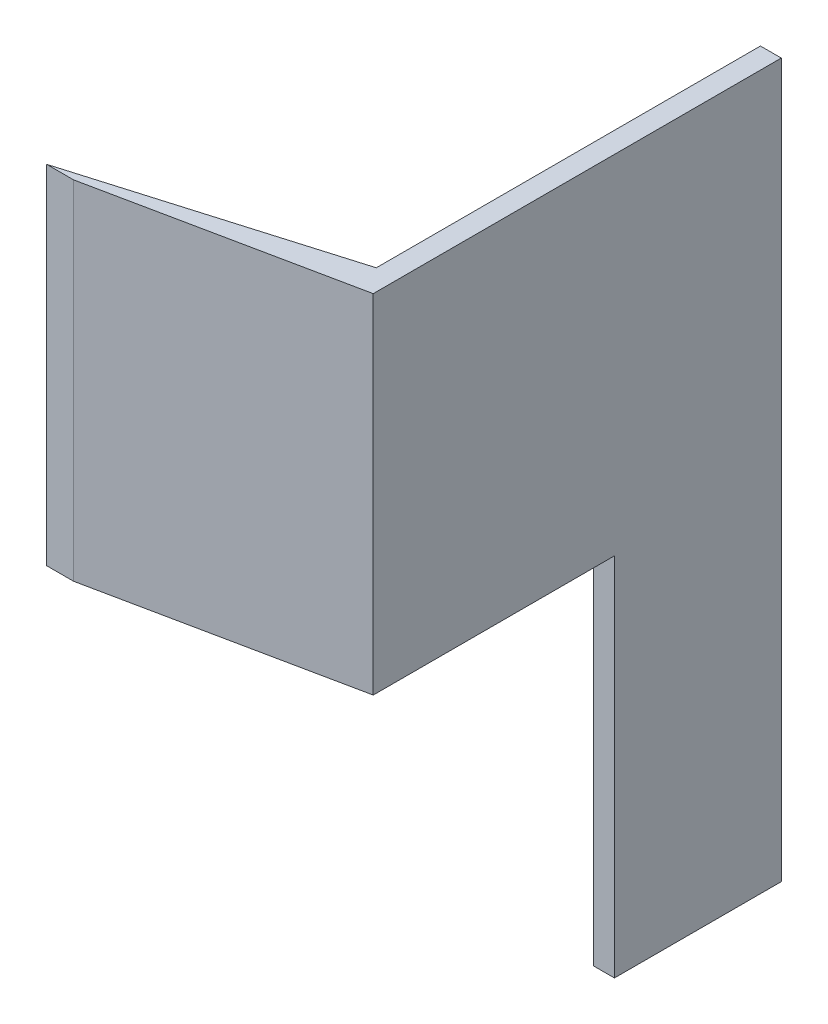
SolidWorks part; units mm, degrees
material "Perspex (TM) GS Acrylic Cast Sheet"
ref_plane "Front Plane" through (0, 0, 0) normal (0, 0, 1) x (1, 0, 0)
ref_plane "Top Plane" through (0, 0, 0) normal (0, 1, 0) x (1, 0, 0)
ref_plane "Right Plane" through (0, 0, 0) normal (1, 0, 0) x (0, 0, -1)
sketch "Sketch1" plane through (0, 0, 0) normal (0, 1, 0) x (1, 0, 0)
  line L0 (0, 46.72) -> (0, 0) construction
  line L2 (3, 0) -> (3, 46.72)
  line L3 (3, 46.72) -> (0, 46.72) construction
  line L4 (-8.1614, -11.8261) -> (-33.5868, -19.3412)
  line L5 (-29.7248, -19.3412) -> (-7.554, -14.764)
  line L6 (-33.5868, -19.3412) -> (-29.7248, -19.3412)
  line L7 (0.0002, -0.0334) -> (3, 0) construction
  line L8 (0, 0) -> (0.0002, -0.0334)
  line L9 (3, -8.5271) -> (3, 0)
  line L10 (-8.1614, -11.8261) -> (3, -8.5271)
  line L11 (-7.554, -14.764) -> (6, -11.9658)
  line L13 (3, 46.72) -> (6, 46.72)
  line L14 (6, 46.72) -> (6, -11.9658)
  spline S0 degree 1 poles (0.0002, -0.0334) (-8.1614, -11.8261) knots 0 0 1 1 construction
  spline S1 degree 2 poles (3, 0) (3.1399, -12.5531) (-7.554, -14.764) knots 0 0 0 1 1 1 construction
  spline S2 degree 3 poles (0.0002, -0.0334) (0.0052, -0.4868) (-0.0095, -1.4173) (-0.1374, -3.0879) (-0.4716, -4.9478) (-1.1168, -6.7822) (-1.9737, -8.2695) (-3.0429, -9.4773) (-4.3717, -10.472) (-5.7648, -11.143) (-7.0595, -11.5706) (-7.7988, -11.7512) (-8.1614, -11.8261) knots 0 0 0 0 0.0625 0.125 0.25 0.375 0.5 0.625 0.75 0.875 0.9375 1 1 1 1 construction
  point P14 (5.9557, -12.1893)
  point P15 (6, 46.72)
  dimension "D2" = 3
  dimension "D4" = 0.0002
  dimension "D5" = 1.6895
  dimension "D6" = 7.554
  dimension "D7" = 8.1614
  dimension "D8" = 29.7248
  dimension "D9" = 33.5868
  dimension "D10" = 19.3412
  dimension "D11" = 46.72
  dimension "D12" = 3
  dimension "D3" = 3
extrude "Boss-Extrude1" add sketch "Sketch1" along normal blind 50 contours L0 L8 L7 L2 L3 | L7 S2 L4 L6 L5 S1 region at (3.7701, 0, -23.36)
sketch "Sketch2" plane through (0, 0, 0) normal (0, -1, 0) x (1, 0, 0)
  line L5 (3, 8.5271) -> (3, -46.72) construction
  line L6 (6, -46.72) -> (3, -46.72)
  line L7 (6, -46.72) -> (6, -22.72)
  line L8 (6, -22.72) -> (3, -22.72)
  line L9 (3, -46.72) -> (3, -22.72)
  dimension "D1" = 24
extrude "Boss-Extrude2" add sketch "Sketch2" along normal blind 52.58
sketch "Sketch3" plane through (6, 0, 0) normal (1, 0, 0) x (0, 0, -1)
  line L0 (34.72, -40.08) -> (34.72, 32.3628) construction
  line L1 (46.72, 50) -> (46.72, -52.58) construction
  line L2 (46.72, -52.58) -> (22.72, -52.58) construction
  dimension "D1" = 12
  dimension "D2" = 12.5
